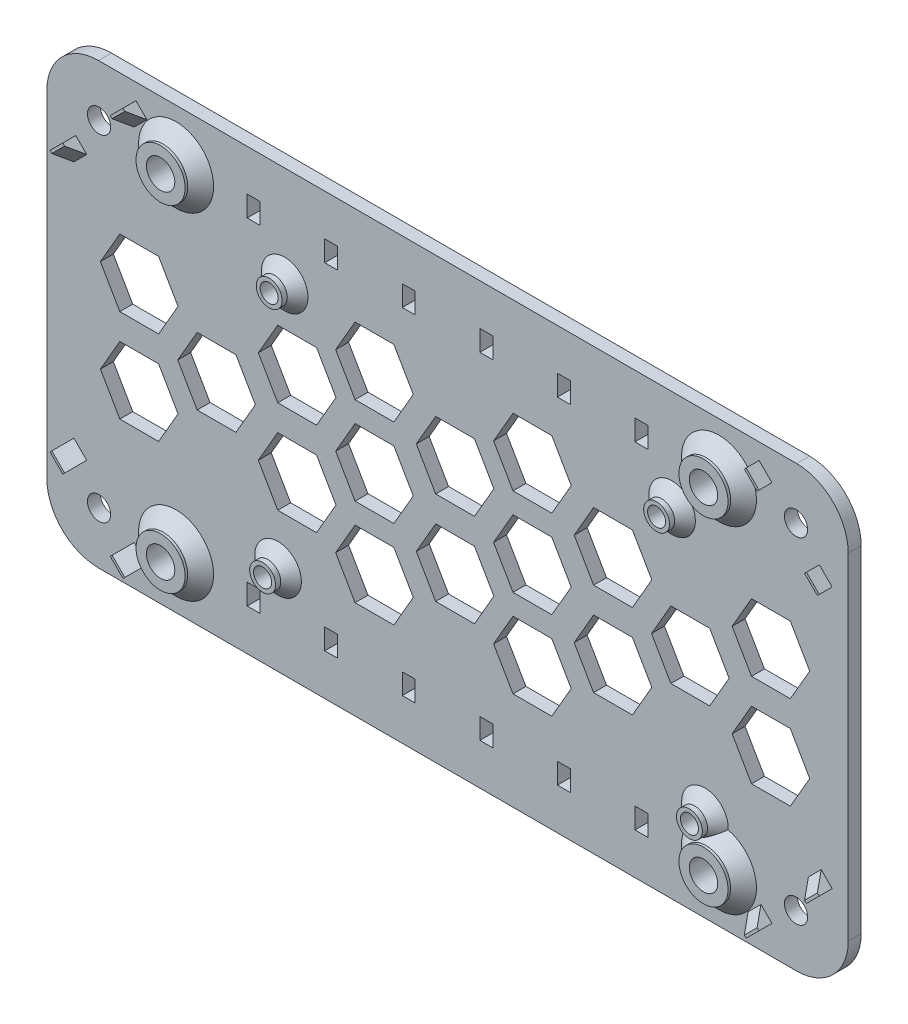
SolidWorks part; units mm, degrees
ref_plane "Front Plane" through (0, 0, 0) normal (0, 0, 1) x (1, 0, 0)
ref_plane "Top Plane" through (0, 0, 0) normal (0, 1, 0) x (1, 0, 0)
ref_plane "Right Plane" through (0, 0, 0) normal (1, 0, 0) x (0, 0, -1)
sketch "Sketch1" plane through (0, 0, 0) normal (0, 0, 1) x (1, 0, 0)
  line L1 (-70, 42.5) -> (65, 42.5)
  line L2 (-80, 32.5) -> (-80, -32.5)
  line L3 (-70, -42.5) -> (65, -42.5)
  line L4 (75, 32.5) -> (75, -32.5)
  arc A0 (-80, -32.5) -> (-70, -42.5) centre (-70, -32.5) ccw
  arc A1 (65, -42.5) -> (75, -32.5) centre (65, -32.5) ccw
  arc A2 (65, 42.5) -> (75, 32.5) centre (65, 32.5) cw
  arc A3 (-70, 42.5) -> (-80, 32.5) centre (-70, 32.5) ccw
  point P1 (0, 0)
  dimension "D4" = 10
  dimension "D1" = 85
  dimension "D2" = 155
extrude "main" add sketch "Sketch1" along normal blind 2.5
sketch "Sketch2" plane through (0, 0, 0) normal (0, 0, 1) x (1, 0, 0)
  circle A0 centre (-69.9, -32.4) radius 2.25
  circle A1 centre (-69.9, 32.5) radius 2.25
  circle A2 centre (64.9, 32.5) radius 2.25
  circle A3 centre (64.9, -32.4) radius 2.25
  dimension "D1" = 4.5
extrude "corner_screw" cut sketch "Sketch2" along normal blind 3
sketch "mount_place" plane through (0, 0, 2.5) normal (0, 0, 1) x (1, 0, 0)
  line L0 (65, 42.5) -> (-70, 42.5) construction
  line L1 (-80, 32.5) -> (-80, -32.5) construction
  line L2 (75, -32.5) -> (75, 32.5) construction
  circle A0 centre (-55, 32.5) radius 4.75
  circle A1 centre (50, 32.5) radius 4.75
  circle A2 centre (50, -32.5) radius 4.75
  circle A3 centre (-55, -32.5) radius 4.75
  dimension "D1" = 9.5
  dimension "D2" = 10
  dimension "D3" = 25
  dimension "D4" = 25
extrude "mount_screw" add sketch "mount_place" along normal blind 3
sketch "Sketch9" plane through (0, 0, 2.5) normal (0, 0, 1) x (1, 0, 0)
  circle A0 centre (-33.997, 23.0597) radius 2.5
  circle A1 centre (40.933, 23.0597) radius 2.5
  circle A2 centre (47.283, -25.2003) radius 2.5
  circle A3 centre (-35.267, -25.2003) radius 2.5
  dimension "D1" = 5
extrude "board_screw" add sketch "Sketch9" along normal blind 3
chamfer "Chamfer1" distance 2.5 angle 45 4 edges at (54.75, 32.5, 2.5) (54.75, -32.5, 2.5) (-50.25, -32.5, 2.5) (-50.25, 32.5, 2.5)
sketch "Sketch5" plane through (0, 0, 5.5) normal (0, 0, 1) x (1, 0, 0)
  circle A0 centre (-55, 32.5) radius 2.75
  circle A1 centre (50, 32.5) radius 2.75
  circle A2 centre (-55, -32.5) radius 2.75
  circle A3 centre (50, -32.5) radius 2.75
  dimension "D1" = 5.5
extrude "mount hole" cut sketch "Sketch5" against normal blind 6
sketch "Sketch8" plane through (0, 0, 0) normal (0, 0, -1) x (-1, 0, 0)
  circle A0 centre (-40.933, 23.0597) radius 1.75
  circle A1 centre (33.997, 23.0597) radius 1.75
  circle A2 centre (35.267, -25.2003) radius 1.75
  circle A3 centre (-47.283, -25.2003) radius 1.75
  dimension "D1" = 3.5
extrude "board_hole" cut sketch "Sketch8" against normal blind 6
chamfer "Chamfer2" distance 2 angle 45 4 edges at (46.4109, -22.8573, 2.5) (43.433, 23.0597, 2.5) (-32.767, -25.2003, 2.5) (-31.497, 23.0597, 2.5)
sketch "Sketch10" plane through (0, 0, 0) normal (0, 0, -1) x (-1, 0, 0)
  line L1 (-37.933, 21.3276) -> (-37.933, 24.7917)
  line L2 (-37.933, 24.7917) -> (-40.933, 26.5238)
  line L3 (-40.933, 26.5238) -> (-43.933, 24.7917)
  line L4 (-43.933, 24.7917) -> (-43.933, 21.3276)
  line L5 (-43.933, 21.3276) -> (-40.933, 19.5956)
  line L6 (-40.933, 19.5956) -> (-37.933, 21.3276)
  line L7 (36.997, 21.3276) -> (36.997, 24.7917)
  line L8 (36.997, 24.7917) -> (33.997, 26.5238)
  line L9 (33.997, 26.5238) -> (30.997, 24.7917)
  line L10 (30.997, 24.7917) -> (30.997, 21.3276)
  line L11 (30.997, 21.3276) -> (33.997, 19.5956)
  line L12 (33.997, 19.5956) -> (36.997, 21.3276)
  line L13 (35.267, -28.6644) -> (38.267, -26.9324)
  line L14 (38.267, -26.9324) -> (38.267, -23.4683)
  line L15 (38.267, -23.4683) -> (35.267, -21.7362)
  line L16 (35.267, -21.7362) -> (32.267, -23.4683)
  line L17 (32.267, -23.4683) -> (32.267, -26.9324)
  line L18 (32.267, -26.9324) -> (35.267, -28.6644)
  line L19 (-44.283, -26.9324) -> (-44.283, -23.4683)
  line L20 (-44.283, -23.4683) -> (-47.283, -21.7362)
  line L21 (-47.283, -21.7362) -> (-50.283, -23.4683)
  line L22 (-50.283, -23.4683) -> (-50.283, -26.9324)
  line L23 (-50.283, -26.9324) -> (-47.283, -28.6644)
  line L24 (-47.283, -28.6644) -> (-44.283, -26.9324)
  circle A0 centre (-40.933, 23.0597) radius 3 construction
  circle A1 centre (33.997, 23.0597) radius 3 construction
  circle A2 centre (35.267, -25.2003) radius 3 construction
  circle A3 centre (-47.283, -25.2003) radius 3 construction
  dimension "D1" = 6
extrude "nuts" cut sketch "Sketch10" against normal blind 2.5
sketch "Sketch11" plane through (0, 0, 2.5) normal (0, 0, 1) x (1, 0, 0)
  line L0 (-65.2347, -36.9118) -> (-62.7598, -39.3867)
  line L1 (-65.2347, -36.9118) -> (-63.1133, -34.7905)
  line L2 (-62.7598, -39.3867) -> (-60.6385, -37.2653)
  line L3 (-63.1133, -34.7905) -> (-60.6385, -37.2653)
  line L4 (-74.4118, -27.7347) -> (-76.8867, -25.2598)
  line L5 (-74.4118, -27.7347) -> (-72.2905, -25.6133)
  line L6 (-76.8867, -25.2598) -> (-74.7653, -23.1385)
  line L7 (-72.2905, -25.6133) -> (-74.7653, -23.1385)
  line L10 (75, 0) -> (-80, 0) construction
  line L11 (-80, 32.5) -> (-80, -32.5) construction
  line L12 (75, -32.5) -> (75, 32.5) construction
  line L14 (-72.2905, 25.6133) -> (-74.7653, 23.1385)
  line L15 (-76.8867, 25.2598) -> (-74.7653, 23.1385)
  line L16 (-74.4118, 27.7347) -> (-72.2905, 25.6133)
  line L17 (-74.4118, 27.7347) -> (-76.8867, 25.2598)
  line L18 (-63.1133, 34.7905) -> (-60.6385, 37.2653)
  line L19 (-62.7598, 39.3867) -> (-60.6385, 37.2653)
  line L20 (-65.2347, 36.9118) -> (-63.1133, 34.7905)
  line L21 (-65.2347, 36.9118) -> (-62.7598, 39.3867)
  line L22 (-2.5, 42.5) -> (-2.5, -42.5) construction
  line L23 (65, 42.5) -> (-70, 42.5) construction
  line L24 (-70, -42.5) -> (65, -42.5) construction
  line L25 (60.2347, 36.9118) -> (57.7598, 39.3867)
  line L26 (60.2347, 36.9118) -> (58.1133, 34.7905)
  line L27 (57.7598, 39.3867) -> (55.6385, 37.2653)
  line L28 (58.1133, 34.7905) -> (55.6385, 37.2653)
  line L29 (69.4118, 27.7347) -> (71.8867, 25.2598)
  line L30 (69.4118, 27.7347) -> (67.2905, 25.6133)
  line L31 (71.8867, 25.2598) -> (69.7653, 23.1385)
  line L32 (67.2905, 25.6133) -> (69.7653, 23.1385)
  line L33 (67.2905, -25.6133) -> (69.7653, -23.1385)
  line L34 (71.8867, -25.2598) -> (69.7653, -23.1385)
  line L35 (69.4118, -27.7347) -> (67.2905, -25.6133)
  line L36 (69.4118, -27.7347) -> (71.8867, -25.2598)
  line L37 (58.1133, -34.7905) -> (55.6385, -37.2653)
  line L38 (57.7598, -39.3867) -> (55.6385, -37.2653)
  line L39 (60.2347, -36.9118) -> (58.1133, -34.7905)
  line L40 (60.2347, -36.9118) -> (57.7598, -39.3867)
  line L42 (-74.235, -28.265) -> (-77.5, -25) construction
  dimension "D1" = 3.5
  dimension "D2" = 0.5
  dimension "D3" = 0.5
  dimension "D4" = 3
  dimension "D5" = 0.25
extrude "corner_stoppers" add sketch "Sketch11" along normal blind 2.5
chamfer "Chamfer3" distance 2.5 angle 45 8 edges at (68.5279, -24.3759, 5) (56.8759, -36.0279, 5) (56.8759, 36.0279, 5) (68.5279, 24.3759, 5) (-61.8759, -36.0279, 5) (-73.5279, 24.3759, 5) (-73.5279, -24.3759, 5) (-61.8759, 36.0279, 5)
sketch "Sketch16" plane through (0, 0, 2.5) normal (0, 0, 1) x (1, 0, 0)
  line L0 (44.4562, 0) -> (60.0447, 9) construction
  line L1 (51.9617, 0) -> (48.209, 6.5)
  line L2 (48.209, 6.5) -> (40.7034, 6.5)
  line L3 (40.7034, 6.5) -> (36.9506, 0)
  line L4 (36.9506, 0) -> (40.7034, -6.5)
  line L5 (40.7034, -6.5) -> (48.209, -6.5)
  line L6 (48.209, -6.5) -> (51.9617, 0)
  line L7 (67.5502, 9) -> (63.7974, 15.5)
  line L8 (63.7974, 15.5) -> (56.2919, 15.5)
  line L9 (56.2919, 15.5) -> (52.5391, 9)
  line L10 (52.5391, 9) -> (56.2919, 2.5)
  line L11 (56.2919, 2.5) -> (63.7974, 2.5)
  line L12 (63.7974, 2.5) -> (67.5502, 9)
  line L13 (67.5502, -9) -> (63.7974, -2.5)
  line L14 (63.7974, -2.5) -> (56.2919, -2.5)
  line L15 (56.2919, -2.5) -> (52.5391, -9)
  line L16 (52.5391, -9) -> (56.2919, -15.5)
  line L17 (56.2919, -15.5) -> (63.7974, -15.5)
  line L18 (63.7974, -15.5) -> (67.5502, -9)
  line L19 (60.0447, 9) -> (60.0447, -9) construction
  line L20 (60.0447, -9) -> (44.4562, 0) construction
  line L21 (-80, 0) -> (75, 0) construction
  line L22 (-80, 32.5) -> (-80, -32.5) construction
  line L23 (75, -32.5) -> (75, 32.5) construction
  line L24 (21.4179, 0) -> (17.6652, 6.5)
  line L25 (17.6652, 6.5) -> (10.1596, 6.5)
  line L26 (10.1596, 6.5) -> (6.4068, 0)
  line L27 (6.4068, 0) -> (10.1596, -6.5)
  line L28 (10.1596, -6.5) -> (17.6652, -6.5)
  line L29 (17.6652, -6.5) -> (21.4179, 0)
  line L30 (37.0064, 9) -> (33.2536, 15.5)
  line L31 (33.2536, 15.5) -> (25.7481, 15.5)
  line L32 (25.7481, 15.5) -> (21.9953, 9)
  line L33 (21.9953, 9) -> (25.7481, 2.5)
  line L34 (25.7481, 2.5) -> (33.2536, 2.5)
  line L35 (33.2536, 2.5) -> (37.0064, 9)
  line L36 (37.0064, -9) -> (33.2536, -2.5)
  line L37 (33.2536, -2.5) -> (25.7481, -2.5)
  line L38 (25.7481, -2.5) -> (21.9953, -9)
  line L39 (21.9953, -9) -> (25.7481, -15.5)
  line L40 (25.7481, -15.5) -> (33.2536, -15.5)
  line L41 (33.2536, -15.5) -> (37.0064, -9)
  line L42 (13.9124, 0) -> (29.5008, 9) construction
  line L43 (29.5008, 9) -> (29.5008, -9) construction
  line L44 (29.5008, -9) -> (13.9124, 0) construction
  line L46 (-9.1259, 0) -> (-12.8786, 6.5)
  line L47 (-12.8786, 6.5) -> (-20.3842, 6.5)
  line L48 (-20.3842, 6.5) -> (-24.137, 0)
  line L49 (-24.137, 0) -> (-20.3842, -6.5)
  line L50 (-20.3842, -6.5) -> (-12.8786, -6.5)
  line L51 (-12.8786, -6.5) -> (-9.1259, 0)
  line L52 (6.4626, 9) -> (2.7098, 15.5)
  line L53 (2.7098, 15.5) -> (-4.7957, 15.5)
  line L54 (-4.7957, 15.5) -> (-8.5485, 9)
  line L55 (-8.5485, 9) -> (-4.7957, 2.5)
  line L56 (-4.7957, 2.5) -> (2.7098, 2.5)
  line L57 (2.7098, 2.5) -> (6.4626, 9)
  line L58 (6.4626, -9) -> (2.7098, -2.5)
  line L59 (2.7098, -2.5) -> (-4.7957, -2.5)
  line L60 (-4.7957, -2.5) -> (-8.5485, -9)
  line L61 (-8.5485, -9) -> (-4.7957, -15.5)
  line L62 (-4.7957, -15.5) -> (2.7098, -15.5)
  line L63 (2.7098, -15.5) -> (6.4626, -9)
  line L64 (-16.6314, 0) -> (-1.043, 9) construction
  line L65 (-1.043, 9) -> (-1.043, -9) construction
  line L66 (-1.043, -9) -> (-16.6314, 0) construction
  line L68 (-39.6697, 0) -> (-43.4224, 6.5)
  line L69 (-43.4224, 6.5) -> (-50.928, 6.5)
  line L70 (-50.928, 6.5) -> (-54.6808, 0)
  line L71 (-54.6808, 0) -> (-50.928, -6.5)
  line L72 (-50.928, -6.5) -> (-43.4224, -6.5)
  line L73 (-43.4224, -6.5) -> (-39.6697, 0)
  line L74 (-24.0812, 9) -> (-27.834, 15.5)
  line L75 (-27.834, 15.5) -> (-35.3395, 15.5)
  line L76 (-35.3395, 15.5) -> (-39.0923, 9)
  line L77 (-39.0923, 9) -> (-35.3395, 2.5)
  line L78 (-35.3395, 2.5) -> (-27.834, 2.5)
  line L79 (-27.834, 2.5) -> (-24.0812, 9)
  line L80 (-24.0812, -9) -> (-27.834, -2.5)
  line L81 (-27.834, -2.5) -> (-35.3395, -2.5)
  line L82 (-35.3395, -2.5) -> (-39.0923, -9)
  line L83 (-39.0923, -9) -> (-35.3395, -15.5)
  line L84 (-35.3395, -15.5) -> (-27.834, -15.5)
  line L85 (-27.834, -15.5) -> (-24.0812, -9)
  line L86 (-47.1752, 0) -> (-31.5868, 9) construction
  line L87 (-31.5868, 9) -> (-31.5868, -9) construction
  line L88 (-31.5868, -9) -> (-47.1752, 0) construction
  line L96 (-54.625, 9) -> (-58.3778, 15.5)
  line L97 (-58.3778, 15.5) -> (-65.8833, 15.5)
  line L98 (-65.8833, 15.5) -> (-69.6361, 9)
  line L99 (-69.6361, 9) -> (-65.8833, 2.5)
  line L100 (-65.8833, 2.5) -> (-58.3778, 2.5)
  line L101 (-58.3778, 2.5) -> (-54.625, 9)
  line L102 (-54.625, -9) -> (-58.3778, -2.5)
  line L103 (-58.3778, -2.5) -> (-65.8833, -2.5)
  line L104 (-65.8833, -2.5) -> (-69.6361, -9)
  line L105 (-69.6361, -9) -> (-65.8833, -15.5)
  line L106 (-65.8833, -15.5) -> (-58.3778, -15.5)
  line L107 (-58.3778, -15.5) -> (-54.625, -9)
  line L108 (-77.719, 0) -> (-62.1306, 9) construction
  line L109 (-62.1306, 9) -> (-62.1306, -9) construction
  line L110 (-62.1306, -9) -> (-77.719, 0) construction
  line L112 (-24.137, 17) -> (-20.3842, 10.5)
  line L113 (-20.3842, 10.5) -> (-12.8786, 10.5)
  line L114 (-12.8786, 10.5) -> (-9.1259, 17)
  line L115 (-12.8786, 23.5) -> (-20.3842, 23.5)
  line L116 (-20.3842, 23.5) -> (-24.137, 17)
  line L117 (-9.1259, 17) -> (-12.8786, 23.5)
  line L118 (10.1596, 23.5) -> (6.4068, 17)
  line L119 (17.6652, 23.5) -> (10.1596, 23.5)
  line L120 (21.4179, 17) -> (17.6652, 23.5)
  line L121 (17.6652, 10.5) -> (21.4179, 17)
  line L122 (10.1596, 10.5) -> (17.6652, 10.5)
  line L123 (6.4068, 17) -> (10.1596, 10.5)
  line L124 (21.4179, -17) -> (17.6652, -10.5)
  line L125 (17.6652, -10.5) -> (10.1596, -10.5)
  line L126 (10.1596, -10.5) -> (6.4068, -17)
  line L127 (6.4068, -17) -> (10.1596, -23.5)
  line L128 (10.1596, -23.5) -> (17.6652, -23.5)
  line L129 (17.6652, -23.5) -> (21.4179, -17)
  line L133 (-9.1259, -17) -> (-12.8786, -10.5)
  line L134 (-12.8786, -10.5) -> (-20.3842, -10.5)
  line L135 (-20.3842, -10.5) -> (-24.137, -17)
  line L136 (-24.137, -17) -> (-20.3842, -23.5)
  line L137 (-20.3842, -23.5) -> (-12.8786, -23.5)
  line L138 (-12.8786, -23.5) -> (-9.1259, -17)
  line L143 (-80, -17) -> (75, -17) construction
  line L144 (-202.1752, 0) -> (-47.1752, 0) construction
  line L145 (-171.6314, 0) -> (-16.6314, 0) construction
  line L146 (-141.0876, 0) -> (13.9124, 0) construction
  line L147 (-110.5438, 0) -> (44.4562, 0) construction
  line L148 (-70.2135, 0) -> (-73.9662, 6.5) construction
  line L149 (-73.9662, 6.5) -> (-81.4718, 6.5) construction
  line L150 (-81.4718, 6.5) -> (-85.2246, 0) construction
  line L151 (-85.2246, 0) -> (-81.4718, -6.5) construction
  line L152 (-81.4718, -6.5) -> (-73.9662, -6.5) construction
  line L153 (-73.9662, -6.5) -> (-70.2135, 0) construction
  circle A0 centre (44.4562, 0) radius 6.5 construction
  circle A1 centre (60.0447, 9) radius 6.5 construction
  circle A2 centre (60.0447, -9) radius 6.5 construction
  circle A3 centre (13.9124, 0) radius 6.5 construction
  circle A4 centre (29.5008, 9) radius 6.5 construction
  circle A5 centre (29.5008, -9) radius 6.5 construction
  circle A6 centre (-16.6314, 0) radius 6.5 construction
  circle A7 centre (-1.043, 9) radius 6.5 construction
  circle A8 centre (-1.043, -9) radius 6.5 construction
  circle A9 centre (-47.1752, 0) radius 6.5 construction
  circle A10 centre (-31.5868, 9) radius 6.5 construction
  circle A11 centre (-31.5868, -9) radius 6.5 construction
  circle A13 centre (-62.1306, 9) radius 6.5 construction
  circle A14 centre (-62.1306, -9) radius 6.5 construction
  circle A15 centre (13.9124, -17) radius 6.5 construction
  circle A16 centre (-16.6314, -17) radius 6.5 construction
  circle A17 centre (-77.719, 0) radius 6.5 construction
  dimension "D1" = 13
  dimension "D2" = 5
  dimension "D3" = 5
  dimension "D4" = 2
  dimension "D5" = 2
extrude "decor" cut sketch "Sketch16" against normal blind 3
sketch "Sketch17" plane through (0, 0, 2.5) normal (0, 0, 1) x (1, 0, 0)
  line L0 (50, 32.5) -> (-55, 32.5) construction
  line L1 (21.25, 30.5) -> (18.75, 30.5)
  line L2 (36.25, 30.5) -> (33.75, 30.5)
  line L3 (36.25, 30.5) -> (36.25, 34.5)
  line L4 (36.25, 34.5) -> (33.75, 34.5)
  line L5 (33.75, 30.5) -> (33.75, 34.5)
  line L6 (36.25, 30.5) -> (33.75, 34.5) construction
  line L7 (36.25, 34.5) -> (33.75, 30.5) construction
  line L8 (21.25, 30.5) -> (21.25, 34.5)
  line L9 (-55, 32.5) -> (-55, -32.5) construction
  line L10 (-55, -32.5) -> (50, -32.5) construction
  line L11 (50, -32.5) -> (50, 32.5) construction
  line L12 (21.25, 34.5) -> (18.75, 34.5)
  line L13 (18.75, 30.5) -> (18.75, 34.5)
  line L14 (21.25, 30.5) -> (18.75, 34.5) construction
  line L15 (21.25, 34.5) -> (18.75, 30.5) construction
  line L16 (6.25, 30.5) -> (3.75, 30.5)
  line L17 (6.25, 30.5) -> (6.25, 34.5)
  line L18 (6.25, 34.5) -> (3.75, 34.5)
  line L19 (3.75, 30.5) -> (3.75, 34.5)
  line L20 (6.25, 30.5) -> (3.75, 34.5) construction
  line L21 (6.25, 34.5) -> (3.75, 30.5) construction
  line L22 (-8.75, 30.5) -> (-11.25, 30.5)
  line L23 (-8.75, 30.5) -> (-8.75, 34.5)
  line L24 (-8.75, 34.5) -> (-11.25, 34.5)
  line L25 (-11.25, 30.5) -> (-11.25, 34.5)
  line L26 (-8.75, 30.5) -> (-11.25, 34.5) construction
  line L27 (-8.75, 34.5) -> (-11.25, 30.5) construction
  line L28 (-23.75, 30.5) -> (-26.25, 30.5)
  line L29 (-23.75, 30.5) -> (-23.75, 34.5)
  line L30 (-23.75, 34.5) -> (-26.25, 34.5)
  line L31 (-26.25, 30.5) -> (-26.25, 34.5)
  line L32 (-23.75, 30.5) -> (-26.25, 34.5) construction
  line L33 (-23.75, 34.5) -> (-26.25, 30.5) construction
  line L34 (-38.75, 30.5) -> (-41.25, 30.5)
  line L35 (-38.75, 30.5) -> (-38.75, 34.5)
  line L36 (-38.75, 34.5) -> (-41.25, 34.5)
  line L37 (-41.25, 30.5) -> (-41.25, 34.5)
  line L38 (-38.75, 30.5) -> (-41.25, 34.5) construction
  line L39 (-38.75, 34.5) -> (-41.25, 30.5) construction
  line L40 (21.25, -34.5) -> (18.75, -34.5)
  line L41 (36.25, -34.5) -> (33.75, -34.5)
  line L42 (36.25, -34.5) -> (36.25, -30.5)
  line L43 (36.25, -30.5) -> (33.75, -30.5)
  line L44 (33.75, -34.5) -> (33.75, -30.5)
  line L45 (21.25, -34.5) -> (21.25, -30.5)
  line L46 (21.25, -30.5) -> (18.75, -30.5)
  line L47 (18.75, -34.5) -> (18.75, -30.5)
  line L48 (6.25, -34.5) -> (3.75, -34.5)
  line L49 (6.25, -34.5) -> (6.25, -30.5)
  line L50 (6.25, -30.5) -> (3.75, -30.5)
  line L51 (3.75, -34.5) -> (3.75, -30.5)
  line L52 (-8.75, -34.5) -> (-11.25, -34.5)
  line L53 (-8.75, -34.5) -> (-8.75, -30.5)
  line L54 (-8.75, -30.5) -> (-11.25, -30.5)
  line L55 (-11.25, -34.5) -> (-11.25, -30.5)
  line L56 (-23.75, -34.5) -> (-26.25, -34.5)
  line L57 (-23.75, -34.5) -> (-23.75, -30.5)
  line L58 (-23.75, -30.5) -> (-26.25, -30.5)
  line L59 (-26.25, -34.5) -> (-26.25, -30.5)
  line L60 (-38.75, -34.5) -> (-41.25, -34.5)
  line L61 (-38.75, -34.5) -> (-38.75, -30.5)
  line L62 (-38.75, -30.5) -> (-41.25, -30.5)
  line L63 (-41.25, -34.5) -> (-41.25, -30.5)
  line L64 (36.25, -34.5) -> (33.75, -30.5) construction
  line L65 (36.25, -30.5) -> (33.75, -34.5) construction
  line L66 (21.25, -34.5) -> (18.75, -30.5) construction
  line L67 (21.25, -30.5) -> (18.75, -34.5) construction
  line L68 (6.25, -34.5) -> (3.75, -30.5) construction
  line L69 (6.25, -30.5) -> (3.75, -34.5) construction
  line L70 (-8.75, -34.5) -> (-11.25, -30.5) construction
  line L71 (-8.75, -30.5) -> (-11.25, -34.5) construction
  line L72 (-23.75, -34.5) -> (-26.25, -30.5) construction
  line L73 (-23.75, -30.5) -> (-26.25, -34.5) construction
  line L74 (-38.75, -34.5) -> (-41.25, -30.5) construction
  line L75 (-38.75, -30.5) -> (-41.25, -34.5) construction
  circle A0 centre (50, 32.5) radius 7.25 construction
  point P0 (35, 32.5)
  point P12 (35, -32.5)
  point P17 (20, 32.5)
  point P22 (5, 32.5)
  point P27 (-10, 32.5)
  point P32 (-25, 32.5)
  point P37 (-40, 32.5)
  point P47 (20, -32.5)
  point P52 (5, -32.5)
  point P57 (-10, -32.5)
  point P62 (-25, -32.5)
  point P67 (-40, -32.5)
  dimension "D3" = 15
  dimension "D1" = 2.5
  dimension "D2" = 4
  dimension "D4" = 6
  dimension "D5" = 2
extrude "wire_holes" cut sketch "Sketch17" against normal blind 4
